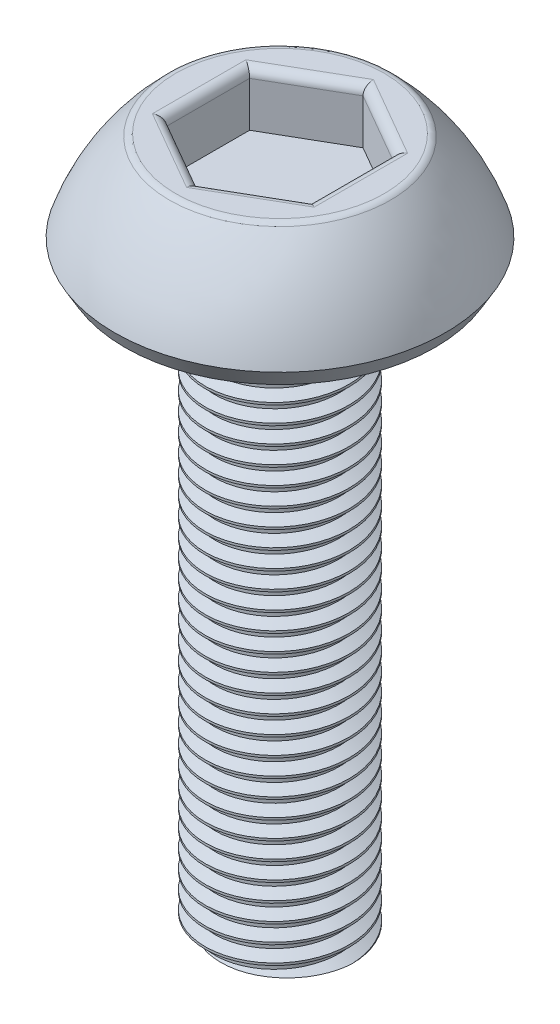
SolidWorks part; units mm, degrees
ref_plane "Front Plane" through (0, 0, 0) normal (0, 0, 1) x (1, 0, 0)
ref_plane "Top Plane" through (0, 0, 0) normal (0, 1, 0) x (1, 0, 0)
ref_plane "Right Plane" through (0, 0, 0) normal (1, 0, 0) x (0, 0, -1)
sketch "Sketch1" plane through (0, 0, 0) normal (1, 0, 0) x (0, 0, -1)
  line L0 (0, 0) -> (0, 1.5) construction
  line L1 (0, 1.5) -> (-1.5, 1.5)
  line L3 (-2.3, 0.25) -> (-2.1557, 0)
  line L4 (-2.1557, 0) -> (-1, 0)
  line L5 (-1, 0) -> (-1, -8)
  line L6 (-1, -8) -> (0, -8)
  line L7 (0, -8) -> (0, 1.5)
  line L8 (0, 0) -> (-1, 0) construction
  arc A0 (-1.5, 1.5) -> (-2.3, 0.25) centre (0.5483, -0.6919) ccw
  dimension "D5" = 3
  dimension "D1" = 1.5
  dimension "D2" = 2.3
  dimension "D3" = 1.5
  dimension "D4" = 0.25
  dimension "D6" = 60
  dimension "D7" = 1
  dimension "D8" = 8
  dimension "D9" = 2.3
revolve "Revolve1" add sketch "Sketch1" angle 360 about L7
sketch "Sketch2" plane through (0, 1.5, 0) normal (0, 1, 0) x (1, 0, 0)
  line L1 (0, 1.1547) -> (-1, 0.5774)
  line L2 (-1, 0.5774) -> (-1, -0.5774)
  line L3 (-1, -0.5774) -> (0, -1.1547)
  line L4 (0, -1.1547) -> (1, -0.5774)
  line L5 (1, -0.5774) -> (1, 0.5774)
  line L6 (1, 0.5774) -> (0, 1.1547)
  circle A0 centre (0, 0) radius 1 construction
  dimension "D1" = 2
extrude "Cut-Extrude1" cut sketch "Sketch2" against normal blind 0.75
fillet "Fillet1" radius 0.125 7 edges at (0, 1.5, -1.5) (-0.5, 1.5, 0.866) (0.5, 1.5, 0.866) (1, 1.5, 0) (0.5, 1.5, -0.866) (-0.5, 1.5, -0.866) (-1, 1.5, 0)
thread "Thread1" pitch 0.25 method cut profile "Thread Profile1" start angle 0, offset 1, length 8.75, pitch 0.25, diameter 2
ref_plane "Plane1" through (1, -9, 0) normal (0, 0, 1) x (1, 0, 0)
sketch "Thread Profile1" plane through (1, -9, 0) normal (0, 0, 1) x (1, 0, 0)
  line L0 (0, 0) -> (0, 0.25) construction
  line L11 (0, 0) -> (0, 0.2187)
  line L12 (0, 0.2187) -> (-0.1353, 0.1406)
  line L13 (-0.1353, 0.1406) -> (-0.1353, 0.0781)
  line L15 (-0.1353, 0.0781) -> (0, 0)
  line L17 (-0.1353, 0.1094) -> (0, 0.1094) construction
  point P2 (0, 0)
  dimension "Pitch" = 0.25
  dimension "Profile_Angle" = 60
  dimension "Profile_Land" = 0.0625
  dimension "Profile_Height" = 0.1353
